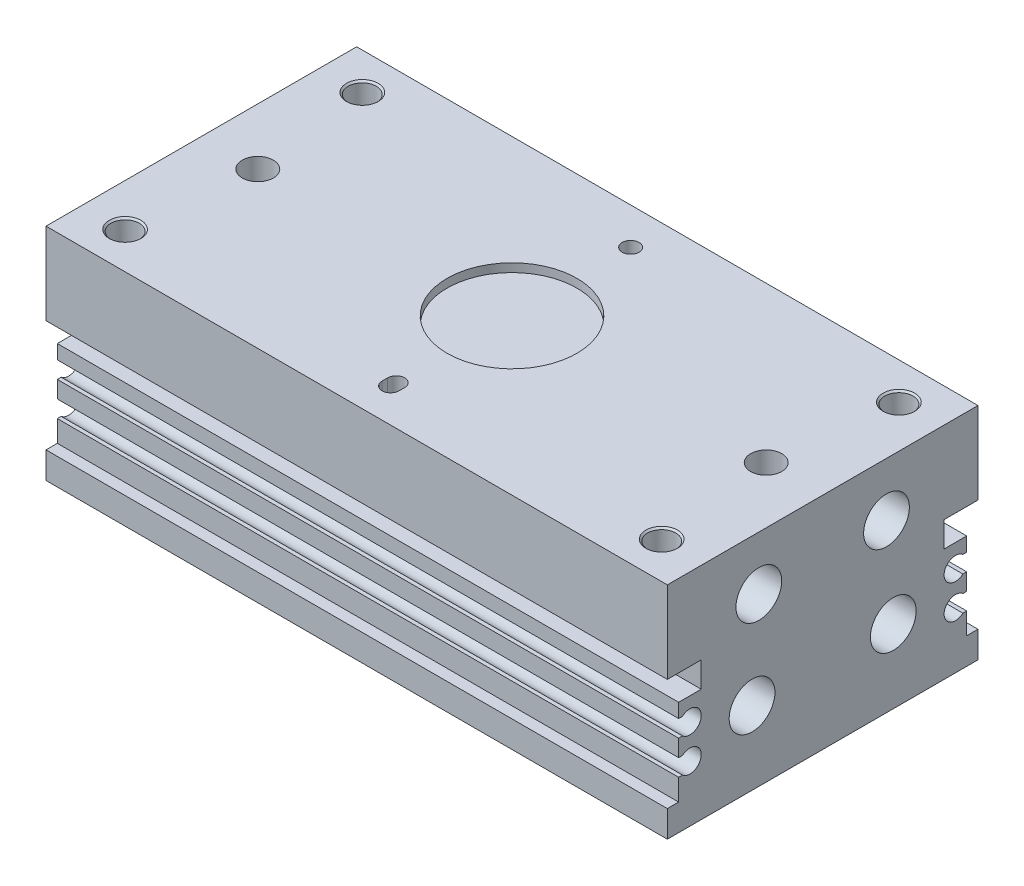
SolidWorks part; units mm, degrees
ref_plane "Front" through (0, 0, 0) normal (0, 0, 1) x (1, 0, 0)
ref_plane "Top" through (0, 0, 0) normal (0, 1, 0) x (1, 0, 0)
ref_plane "Right" through (0, 0, 0) normal (1, 0, 0) x (0, 0, -1)
ref_axis "X" through (-46.75, 0, 0) along (1, 0, 0)
sketch "Sketch2" plane through (0, 0, 0) normal (1, 0, 0) x (0, 0, -1)
  line L1 (-27.5, 19.5) -> (27.5, 19.5)
  line L2 (-27.5, 19.5) -> (-27.5, -19.5)
  line L3 (-27.5, -19.5) -> (27.5, -19.5)
  line L4 (27.5, 19.5) -> (27.5, -19.5)
  dimension "D1" = 39
  dimension "D2" = 55
  dimension "D3" = 19.5
  dimension "D4" = 27.5
extrude "Boss-Extrude1" add sketch "Sketch2" along normal mid plane 110
sketch "Sketch3" plane through (0, 0, 0) normal (1, 0, 0) x (0, 0, -1)
  line L0 (-27.5, 19.5) -> (-27.5, -19.5) construction
  line L1 (-27.5, 5) -> (-25.5, 5)
  line L2 (-27.5, 5) -> (-27.5, -14.8)
  line L3 (-27.5, -14.8) -> (-25.5, -14.8)
  line L4 (-25.5, 5) -> (-25.5, -14.8)
  line L5 (-27.5, -19.5) -> (27.5, -19.5) construction
  line L6 (27.5, -19.5) -> (27.5, 19.5) construction
  line L7 (27.5, 5) -> (25.5, 5)
  line L8 (27.5, 5) -> (27.5, -14.8)
  line L9 (27.5, -14.8) -> (25.5, -14.8)
  line L10 (25.5, 5) -> (25.5, -14.8)
  dimension "D1" = 2
  dimension "D2" = 19.8
  dimension "D3" = 4.7
extrude "Cut-Extrude1" cut sketch "Sketch3" against normal through all and the other way through all
sketch "Sketch5" plane through (0, 0, 0) normal (1, 0, 0) x (0, 0, -1)
  line L0 (-23.5, -3.5) -> (-25.5, -3.5) construction
  line L1 (-25.5, -14.8) -> (-25.5, 5) construction
  line L2 (-23.5, -9.5) -> (-25.5, -9.5) construction
  line L4 (-24.8229, -2) -> (-25.5, -2)
  line L5 (-24.8229, -5) -> (-25.5, -5)
  line L6 (-24.8229, -8) -> (-25.5, -8)
  line L7 (-24.8229, -11) -> (-25.5, -11)
  line L8 (-25.5, -2) -> (-25.5, -5)
  line L9 (-23.5, -2) -> (-25.5, -2) construction
  line L10 (-23.5, -5) -> (-25.5, -5) construction
  line L11 (-23.5, -8) -> (-25.5, -8) construction
  line L12 (-23.5, -11) -> (-25.5, -11) construction
  line L13 (-25.5, -8) -> (-25.5, -11)
  line L14 (0, 19.5) -> (0, -19.5) construction
  line L15 (27.5, 19.5) -> (-27.5, 19.5) construction
  line L16 (-27.5, -19.5) -> (27.5, -19.5) construction
  line L17 (23.5, -9.5) -> (25.5, -9.5) construction
  line L18 (23.5, -3.5) -> (25.5, -3.5) construction
  line L19 (25.5, -8) -> (25.5, -11)
  line L20 (25.5, -2) -> (25.5, -5)
  line L21 (24.8229, -11) -> (25.5, -11)
  line L22 (24.8229, -8) -> (25.5, -8)
  line L23 (24.8229, -5) -> (25.5, -5)
  line L24 (24.8229, -2) -> (25.5, -2)
  arc A0 (-24.8229, -11) -> (-24.8229, -8) centre (-23.5, -9.5) ccw
  arc A1 (-24.8229, -5) -> (-24.8229, -2) centre (-23.5, -3.5) ccw
  arc A2 (24.8229, -5) -> (24.8229, -2) centre (23.5, -3.5) cw
  arc A3 (24.8229, -11) -> (24.8229, -8) centre (23.5, -9.5) cw
  dimension "D1" = 4
  dimension "D2" = 23
  dimension "D3" = 6
  dimension "D8" = 2
  dimension "D4" = 1.5
  dimension "D5" = 1.5
  dimension "D6" = 1.5
  dimension "D7" = 1.5
extrude "Cut-Extrude2" cut sketch "Sketch5" against normal through all and the other way through all
sketch "Sketch7" plane through (0, 19.5, 0) normal (0, 1, 0) x (1, 0, 0)
  line L0 (-55, 27.5) -> (55, -27.5) construction
  line L2 (-47.5, -21) -> (47.5, -21) construction
  line L3 (-47.5, -21) -> (-47.5, 21) construction
  line L4 (-47.5, 21) -> (47.5, 21) construction
  line L5 (47.5, -21) -> (47.5, 21) construction
  line L6 (-47.5, -21) -> (47.5, 21) construction
  line L7 (-47.5, 21) -> (47.5, -21) construction
  circle A0 centre (-47.5, 21) radius 2.5
  circle A1 centre (47.5, 21) radius 2.5
  circle A2 centre (47.5, -21) radius 2.5
  circle A3 centre (-47.5, -21) radius 2.5
  point P4 (0, 0)
  dimension "D3" = 5
  dimension "D1" = 95
  dimension "D2" = 42
extrude "Cut-Extrude4" cut sketch "Sketch7" against normal blind 10
chamfer "Chamfer2" distance 0.3 angle 45 4 edges at (-47.5, 19.5, 23.5) (47.5, 19.5, 23.5) (47.5, 19.5, -18.5) (-47.5, 19.5, -18.5)
sketch "Sketch8" plane through (0, 19.5, 0) normal (0, 1, 0) x (1, 0, 0)
  line L0 (-47.5, 21) -> (47.5, 21) construction
  line L1 (-47.5, -21) -> (47.5, -21) construction
  line L2 (0, -21.5) -> (0, -20.5) construction
  line L3 (-1.5, -21.5) -> (-1.5, -20.5)
  line L4 (1.5, -21.5) -> (1.5, -20.5)
  circle A0 centre (0, 21) radius 1.5
  arc A1 (-1.5, -21.5) -> (1.5, -21.5) centre (0, -21.5) ccw
  arc A2 (1.5, -20.5) -> (-1.5, -20.5) centre (0, -20.5) ccw
  point P12 (0, -21)
  dimension "D1" = 3
  dimension "D2" = 1.5
  dimension "D3" = 1
extrude "Cut-Extrude5" cut sketch "Sketch8" against normal blind 3
sketch "Sketch9" plane through (0, 19.5, 0) normal (0, 1, 0) x (1, 0, 0)
  line L0 (-45, 0) -> (45, 0) construction
  line L4 (-45, 0) -> (0, 0) construction
  circle A0 centre (-45, 0) radius 2.75
  circle A1 centre (45, 0) radius 2.75
  dimension "D2" = 5.5
  dimension "D1" = 90
extrude "Cut-Extrude6" cut sketch "Sketch9" against normal through all
sketch "Sketch10" plane through (0, 0, -27.5) normal (0, 0, -1) x (-1, 0, 0)
  line L0 (-39, 9.5) -> (39, 9.5) construction
  line L1 (0, 9.5) -> (0, 19.5) construction
  line L2 (-55, 19.5) -> (55, 19.5) construction
  circle A0 centre (-39, 9.5) radius 2.5
  circle A1 centre (39, 9.5) radius 2.5
  dimension "D1" = 5
  dimension "D2" = 78
  dimension "D3" = 10
extrude "Cut-Extrude7" cut sketch "Sketch10" against normal blind 6
chamfer "Chamfer3" distance 0.3 angle 45 2 edges at (-39, 12, -27.5) (39, 12, -27.5)
sketch "Sketch11" plane through (0, 0, 0) normal (1, 0, 0) x (0, 0, -1)
  line L0 (-11.3, 10) -> (11.3, 10) construction
  line L1 (-12.5, -6.5) -> (12.5, -6.5) construction
  line L2 (0, 10) -> (0, -6.5) construction
  line L3 (27.5, 19.5) -> (-27.5, 19.5) construction
  circle A0 centre (-11.3, 10) radius 4.05
  circle A1 centre (11.3, 10) radius 4.05
  circle A2 centre (-12.5, -6.5) radius 4.05
  circle A3 centre (12.5, -6.5) radius 4.05
  dimension "D1" = 8.1
  dimension "D6" = 8.1
  dimension "D2" = 22.6
  dimension "D3" = 25
  dimension "D4" = 16.5
  dimension "D5" = 9.5
extrude "Cut-Extrude8" cut sketch "Sketch11" against normal through all and the other way through all
sketch "Sketch12" plane through (0, 19.5, 0) normal (0, 1, 0) x (1, 0, 0)
  line L0 (-55, 27.5) -> (55, -27.5) construction
  circle A0 centre (0, 0) radius 11.5
  dimension "D1" = 23
extrude "Cut-Extrude9" cut sketch "Sketch12" against normal blind 1.5
sketch "Sketch13" plane through (0, 0, 0) normal (1, 0, 0) x (0, 0, -1)
  circle A0 centre (-11.3, 10) radius 5
  circle A1 centre (11.3, 10) radius 5
  circle A2 centre (12.5, -6.5) radius 5
  circle A3 centre (-12.5, -6.5) radius 5
  circle A5 centre (-11.3, 10) radius 4.05 construction
  circle A6 centre (-12.5, -6.5) radius 4.05 construction
  dimension "D1" = 0.95
  dimension "D2" = 0.95
extrude "Cut-Extrude10" cut sketch "Sketch13" against normal mid plane 45
sketch "Sketch14" plane through (0, 0, 0) normal (1, 0, 0) x (0, 0, -1)
  line L0 (0, 19.5) -> (0, -19.5) construction
  line L1 (-27.5, 5) -> (-21.5, 5)
  line L2 (-27.5, 5) -> (-27.5, 0.5)
  line L3 (-27.5, 0.5) -> (-21.5, 0.5)
  line L4 (-21.5, 5) -> (-21.5, 0.5)
  line L5 (27.5, 19.5) -> (-27.5, 19.5) construction
  line L6 (-27.5, -19.5) -> (27.5, -19.5) construction
  line L7 (21.5, 5) -> (21.5, 0.5)
  line L8 (27.5, 0.5) -> (21.5, 0.5)
  line L9 (27.5, 5) -> (27.5, 0.5)
  line L10 (27.5, 5) -> (21.5, 5)
  dimension "D1" = 6
  dimension "D2" = 4.5
extrude "Cut-Extrude11" cut sketch "Sketch14" against normal through all and the other way through all
ref_plane "PORT_PLANE" through (0, 9.5, 0) normal (0, 1, 0) x (1, 0, 0)
sketch "Sketch15"
  dimension "D1" = 70
  dimension "D2" = 27.5
sketch_block_instance "PORT_A-1"
sketch_block "PORT_A" parameters "START"=5, "END"=5, "DEPTH"=5, "DRILL"=4.2, "CHAM"=0.5, "D6"=45, "BLIND"=1, "ANGLE"=90
revolve "CLOSING PORT" [suppressed] cut sketch "Sketch15" angle 360 about L0
pattern_linear "OPENING PORT" [suppressed] count 2 spacing 70 along (1, 0, 0) of bodies 113
equation "\"D3@OPENING PORT\"=\"D1@Sketch15\""
